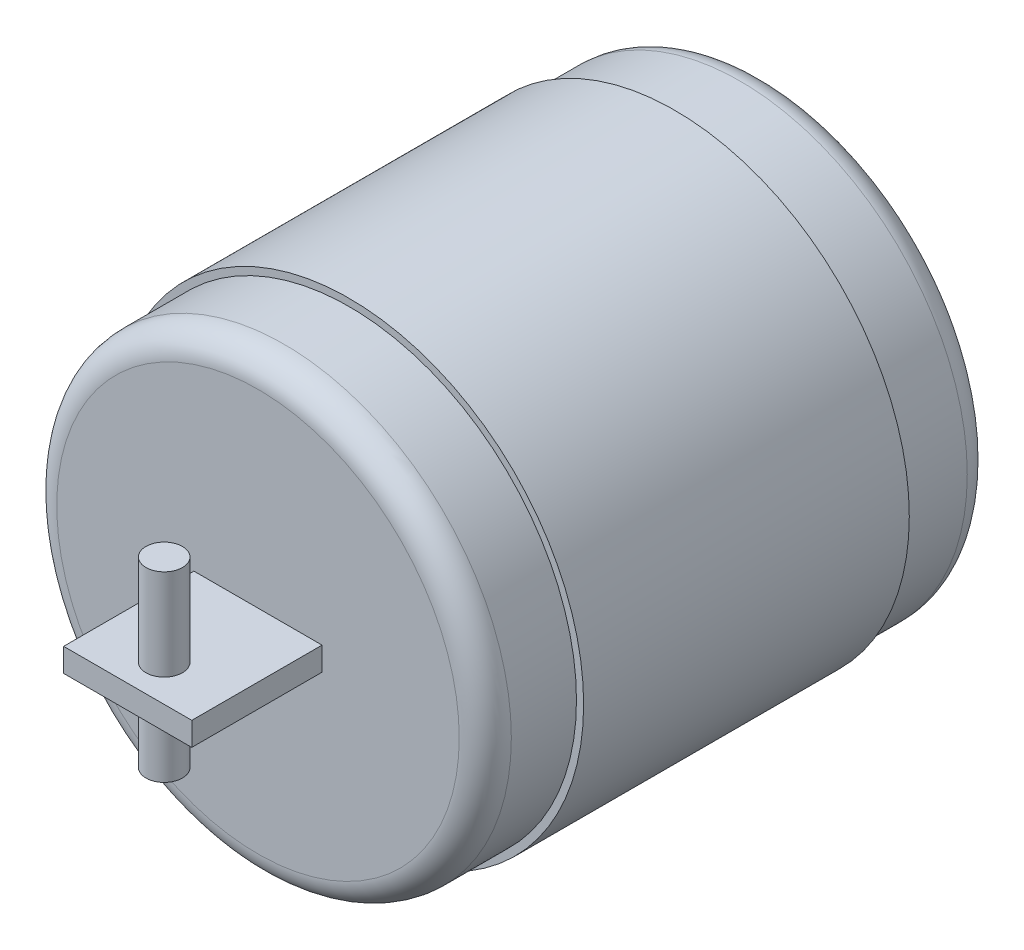
SolidWorks part; units mm, degrees
ref_plane "Front Plane" through (0, 0, 0) normal (0, 0, 1) x (1, 0, 0)
ref_plane "Top Plane" through (0, 0, 0) normal (0, 1, 0) x (1, 0, 0)
ref_plane "Right Plane" through (0, 0, 0) normal (1, 0, 0) x (0, 0, -1)
sketch "Sketch1" plane through (0, 0, 0) normal (0, 0, 1) x (1, 0, 0)
  circle A0 centre (0, 0) radius 18
  dimension "D1" = 36
extrude "Boss-Extrude3" add sketch "Sketch1" along normal blind 25
sketch "Sketch2" plane through (0, 0, 25) normal (0, 0, 1) x (1, 0, 0)
  circle A0 centre (0, 0) radius 17.45
  dimension "D1" = 34.9
extrude "Boss-Extrude4" add sketch "Sketch2" along normal blind 7
extrude "Boss-Extrude5" add sketch "Sketch2<2>" against normal blind 7 from offset 25 offset against normal yes
sketch "Sketch2<2>" plane through (0, 0, 25) normal (0, 0, 1) x (1, 0, 0) same geometry as "Sketch2"
fillet "Fillet1" radius 2 1 edges at (17.45, 0, 32)
fillet "Fillet2" radius 2 1 edges at (17.45, 0, -7)
sketch "Sketch5" plane through (0, 0, -7) normal (0, 0, -1) x (-1, 0, 0)
  point P0 (0, 0)
ref_axis "Axis1" through (0, 0, -31.5764) along (0, 0, 1)
sketch "Sketch7" plane through (0, 0, 32) normal (0, 0, 1) x (1, 0, 0)
  line L1 (-4.9182, 0.9005) -> (4.9182, 0.9005)
  line L2 (-4.9182, 0.9005) -> (-4.9182, -0.9005)
  line L3 (-4.9182, -0.9005) -> (4.9182, -0.9005)
  line L4 (4.9182, 0.9005) -> (4.9182, -0.9005)
  line L5 (-4.9182, 0.9005) -> (4.9182, -0.9005) construction
  line L6 (-4.9182, -0.9005) -> (4.9182, 0.9005) construction
  arc A0 (4.9182, -0.9005) -> (4.9182, 0.9005) centre (0, 0) ccw
  arc A1 (-4.9182, 0.9005) -> (-4.9182, -0.9005) centre (0, 0) ccw
  dimension "D1" = 10
  dimension "D2" = 9.8365
extrude "Boss-Extrude7" add sketch "Sketch7" along normal blind 10 contours L4 L1 L2 L3 region at (0, 0, 32)
sketch "Sketch8" plane through (0, 0.9005, 0) normal (0, 1, 0) x (1, 0, 0)
  line L0 (0, -42) -> (0, -32) construction
  line L1 (-4.9182, -42) -> (4.9182, -42) construction
  line L2 (-4.9182, -32) -> (4.9182, -32) construction
  circle A0 centre (0, -39.2) radius 1.4
  point P7 (-0.4365, -39.2)
  point P9 (0, 0)
  point P10 (0.4449, -39.2)
  point P11 (0, -39.2)
  dimension "D1" = 2.8
  dimension "D2" = 2.8
extrude "Boss-Extrude9" add sketch "Sketch8" along normal blind 7 and the other way blind 7
